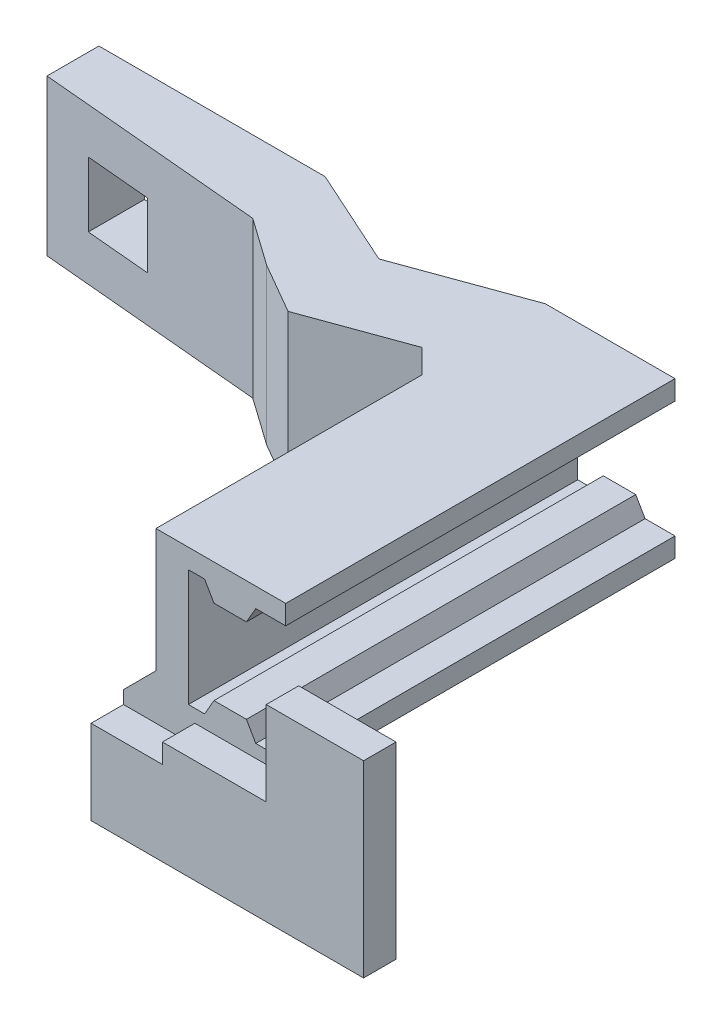
SolidWorks part; units mm, degrees
material "AISI 1045 Steel, cold drawn"
ref_plane "Front Plane" through (0, 0, 0) normal (0, 0, 1) x (1, 0, 0)
ref_plane "Top Plane" through (0, 0, 0) normal (0, 1, 0) x (1, 0, 0)
ref_plane "Right Plane" through (0, 0, 0) normal (1, 0, 0) x (0, 0, -1)
sketch "Sketch1" plane through (0, 0, -109.087) normal (0, 0, 1) x (1, 0, 0)
  line L0 (-916.6698, 150.3705) -> (-916.6698, 153.3705)
  line L1 (-916.6698, 153.3705) -> (-936.6698, 153.3705)
  line L2 (-936.6698, 153.3705) -> (-936.6698, 129.3705)
  line L3 (-936.6698, 129.3705) -> (-916.6698, 129.3705)
  line L4 (-916.6698, 129.3705) -> (-916.6698, 132.3705)
  line L12 (-916.6698, 150.3705) -> (-921.2831, 150.3705)
  line L13 (-921.2831, 150.3705) -> (-922.7265, 147.8705)
  line L14 (-922.7265, 147.8705) -> (-927.7265, 147.8705)
  line L15 (-927.7265, 147.8705) -> (-929.1698, 150.3705)
  line L16 (-929.1698, 150.3705) -> (-931.6698, 150.3705)
  line L17 (-931.6698, 150.3705) -> (-931.6698, 132.3705)
  line L18 (-931.6698, 132.3705) -> (-929.1698, 132.3705)
  line L19 (-929.1698, 132.3705) -> (-927.7265, 134.8705)
  line L20 (-927.7265, 134.8705) -> (-922.7265, 134.8705)
  line L21 (-922.7265, 134.8705) -> (-921.2831, 132.3705)
  line L22 (-921.2831, 132.3705) -> (-916.6698, 132.3705)
  line L23 (-916.6698, 132.3705) -> (-916.6698, 150.3705)
  line L24 (-916.6698, 150.3705) -> (-921.2831, 150.3705)
  line L25 (-921.2831, 150.3705) -> (-922.7265, 147.8705)
  line L26 (-922.7265, 147.8705) -> (-927.7265, 147.8705)
  line L27 (-927.7265, 147.8705) -> (-929.1698, 150.3705)
  line L28 (-929.1698, 150.3705) -> (-931.6698, 150.3705)
  line L29 (-931.6698, 150.3705) -> (-931.6698, 132.3705)
  line L30 (-931.6698, 132.3705) -> (-929.1698, 132.3705)
  line L31 (-929.1698, 132.3705) -> (-927.7265, 134.8705)
  line L32 (-927.7265, 134.8705) -> (-922.7265, 134.8705)
  line L33 (-922.7265, 134.8705) -> (-921.2831, 132.3705)
  line L34 (-921.2831, 132.3705) -> (-916.6698, 132.3705)
  dimension "D2" = 3
  dimension "D3" = 20
  dimension "D4" = 3
  dimension "D1" = 0
extrude "Boss-Extrude1" add sketch "Sketch1" along normal mid plane 60
sketch "Sketch2" plane through (0, 129.3705, 0) normal (0, -1, 0) x (1, 0, 0)
  line L0 (-936.6698, -79.087) -> (-916.6698, -79.087) construction
  line L1 (-930.6698, -79.087) -> (-941.6698, -79.087)
  line L2 (-930.6698, -79.087) -> (-930.6698, -104.087)
  line L3 (-930.6698, -104.087) -> (-941.6698, -104.087)
  line L4 (-941.6698, -79.087) -> (-941.6698, -104.087)
  line L5 (-936.6698, -79.087) -> (-936.6698, -139.087) construction
  dimension "D1" = 25
  dimension "D2" = 5
  dimension "D3" = 6
extrude "Boss-Extrude2" add sketch "Sketch2" along normal blind 15
chamfer "Chamfer1" distance 5 angle 45 2 edges at (-936.6698, 129.3705, -91.587) (-930.6698, 129.3705, -91.587)
sketch "Sketch3" plane through (0, 0, -79.087) normal (0, 0, 1) x (1, 0, 0)
  line L1 (-941.6698, 114.3705) -> (-899.6698, 114.3705)
  line L2 (-941.6698, 114.3705) -> (-941.6698, 127.3705)
  line L3 (-941.6698, 127.3705) -> (-899.6698, 127.3705)
  line L4 (-899.6698, 114.3705) -> (-899.6698, 127.3705)
  dimension "D1" = 42
  dimension "D2" = 13
extrude "Boss-Extrude3" add sketch "Sketch3" along normal blind 5
sketch "Sketch4" plane through (0, 0, -74.087) normal (0, 0, 1) x (1, 0, 0)
  line L0 (-899.6698, 127.3705) -> (-899.6698, 143.3705)
  line L1 (-899.6698, 143.3705) -> (-914.6698, 143.3705)
  line L2 (-914.6698, 143.3705) -> (-914.6698, 130.3705)
  line L3 (-914.6698, 130.3705) -> (-930.6698, 130.3705)
  line L4 (-930.6698, 130.3705) -> (-930.6698, 127.3705)
  line L5 (-899.6698, 127.3705) -> (-941.6698, 127.3705) construction
  line L6 (-930.6698, 127.3705) -> (-899.6698, 127.3705)
  dimension "D1" = 15
  dimension "D2" = 13
  dimension "D3" = 3
  dimension "D4" = 31
extrude "Boss-Extrude4" add sketch "Sketch4" against normal blind 5
sketch "Sketch5" plane through (0, 153.3705, 0) normal (0, 1, 0) x (1, 0, 0)
  line L0 (-936.6698, 139.087) -> (-936.6698, 125.087)
  line L1 (-936.6698, 139.087) -> (-955.4637, 132.2466)
  line L2 (-936.6698, 125.087) -> (-955.4637, 118.2466)
  line L3 (-955.4637, 132.2466) -> (-955.4637, 118.2466)
  line L4 (-936.6698, 79.087) -> (-936.6698, 139.087) construction
  dimension "D1" = 14
  dimension "D2" = 20
  dimension "D3" = 70
extrude "Boss-Extrude5" add sketch "Sketch5" against normal up to surface (24 mm away) up to face at (-926.3365, 129.3705, -107.4203)
chamfer "Chamfer2" distance 5 angle 45 1 edges at (-936.6698, 141.3705, -125.087) first distance on face at (-936.6698, 139.0372, -102.7537)
sketch "Sketch6" plane through (0, 153.3705, 0) normal (0, 1, 0) x (1, 0, 0)
  line L0 (-955.4637, 132.2466) -> (-970.605, 139.087)
  line L1 (-970.605, 139.087) -> (-1005.4637, 139.087)
  line L2 (-1005.4637, 139.087) -> (-1005.4637, 131.087)
  line L3 (-1005.4637, 131.087) -> (-970.605, 127.9447)
  line L4 (-970.605, 127.9447) -> (-963.2579, 122.7466)
  line L5 (-963.2579, 122.7466) -> (-955.4637, 118.2466)
  line L6 (-955.4637, 132.2466) -> (-955.4637, 118.2466) construction
  line L7 (-916.6698, 139.087) -> (-936.6698, 139.087) construction
  line L8 (-970.605, 127.9447) -> (-970.605, 139.087) construction
  line L17 (-916.6698, 139.087) -> (-936.6698, 139.087)
  line L18 (-936.6698, 139.087) -> (-955.4637, 132.2466)
  line L19 (-955.4637, 132.2466) -> (-955.4637, 118.2466)
  line L20 (-955.4637, 118.2466) -> (-940.3356, 123.7528)
  line L21 (-940.3356, 123.7528) -> (-936.6698, 120.087)
  line L22 (-936.6698, 120.087) -> (-936.6698, 79.087)
  line L23 (-936.6698, 79.087) -> (-916.6698, 79.087)
  line L24 (-916.6698, 79.087) -> (-916.6698, 139.087)
  line L27 (-955.4637, 132.2466) -> (-955.4637, 118.2466)
  dimension "D1" = 9
  dimension "D2" = 9
  dimension "D3" = 60
  dimension "D4" = 35
  dimension "D5" = 50
  dimension "D6" = 8
  dimension "D7" = 0
extrude "Boss-Extrude6" add sketch "Sketch6" against normal blind 24
sketch "Sketch7" plane through (0, 0, -139.087) normal (0, 0, -1) x (-1, 0, 0)
  line L0 (970.605, 129.3705) -> (1005.4637, 129.3705) construction
  line L1 (988.4637, 146.3705) -> (998.4637, 146.3705)
  line L2 (988.4637, 146.3705) -> (988.4637, 136.3705)
  line L3 (988.4637, 136.3705) -> (998.4637, 136.3705)
  line L4 (998.4637, 146.3705) -> (998.4637, 136.3705)
  line L5 (988.4637, 146.3705) -> (998.4637, 136.3705) construction
  line L6 (988.4637, 136.3705) -> (998.4637, 146.3705) construction
  line L7 (1005.4637, 129.3705) -> (1005.4637, 153.3705) construction
  point P0 (993.4637, 141.3705)
  dimension "D1" = 10
  dimension "D2" = 10
  dimension "D3" = 7
  dimension "D4" = 7
extrude "Cut-Extrude1" cut sketch "Sketch7" against normal blind 10
